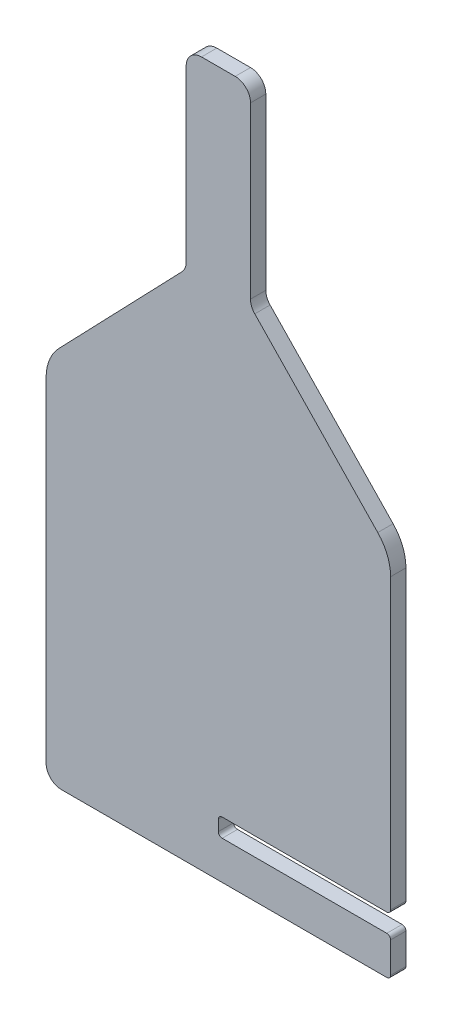
SolidWorks part; units mm, degrees
ref_plane "Alzado" through (0, 0, 0) normal (0, 0, 1) x (1, 0, 0)
ref_plane "Planta" through (0, 0, 0) normal (0, 1, 0) x (1, 0, 0)
ref_plane "Vista lateral" through (0, 0, 0) normal (1, 0, 0) x (0, 0, -1)
sketch "Croquis1" plane through (0, 0, 0) normal (0, 0, 1) x (1, 0, 0)
  line L0 (-4.2, 20) -> (-22.5, 0.9719)
  line L1 (-4.2, 45) -> (4.2, 45)
  line L2 (-22.5, 0.9719) -> (-22.5, -47.0281)
  line L3 (-22.5, -47.0281) -> (22.5, -47.0281)
  line L4 (22.5, 0.9719) -> (22.5, -47.0281)
  line L5 (-4.2, 45) -> (4.2, 45)
  line L6 (-4.2, 45) -> (-4.2, 20)
  line L8 (4.2, 45) -> (4.2, 19.999)
  line L9 (4.2, 19.999) -> (22.5, 0.9719)
  line L10 (0, 72.8664) -> (0, -82.626) construction
  dimension "D1" = 45
  dimension "D2" = 25
  dimension "D3" = 4.2
  dimension "D4" = 22.5
  dimension "D5" = 45
  dimension "D6" = 4.2
  dimension "D7" = 26.3993
  dimension "D8" = 26.4
  dimension "D9" = 48
  dimension "D10" = 48
extrude "Saliente-Extruir1" add sketch "Croquis1" along normal blind 2 contours L6 L0 L2 L3 L4 L9 L8 L1
sketch "Croquis3" plane through (0, 0, 2) normal (0, 0, 1) x (1, 0, 0)
  line L0 (22.5, 0.9719) -> (22.5, -47.0281) construction
  line L1 (22.5, -39.6281) -> (0, -39.6281)
  line L2 (22.5, -39.6281) -> (22.5, -42.0281)
  line L3 (22.5, -42.0281) -> (0, -42.0281)
  line L4 (0, -39.6281) -> (0, -42.0281)
  line L5 (-22.5, -47.0281) -> (22.5, -47.0281) construction
  dimension "D1" = 2.4
  dimension "D2" = 5
  dimension "D3" = 22.5
extrude "Cortar-Extruir2" cut sketch "Croquis3" against normal up to surface (2 mm away) up to face at (0, 4.7358, 0)
fillet "Redondeo1" radius 2 5 edges at (-22.5, -47.0281, 1) (-4.2, 20, 1) (-4.2, 45, 1) (4.2, 19.999, 1) (4.2, 45, 1)
fillet "Redondeo2" radius 6 2 edges at (-22.5, 0.9719, 1) (22.5, 0.9719, 1)
fillet "Redondeo3" radius 0.5 5 edges at (22.5, -47.0281, 1) (0, -42.0281, 1) (0, -39.6281, 1) (22.5, -39.6281, 1) (22.5, -42.0281, 1)
